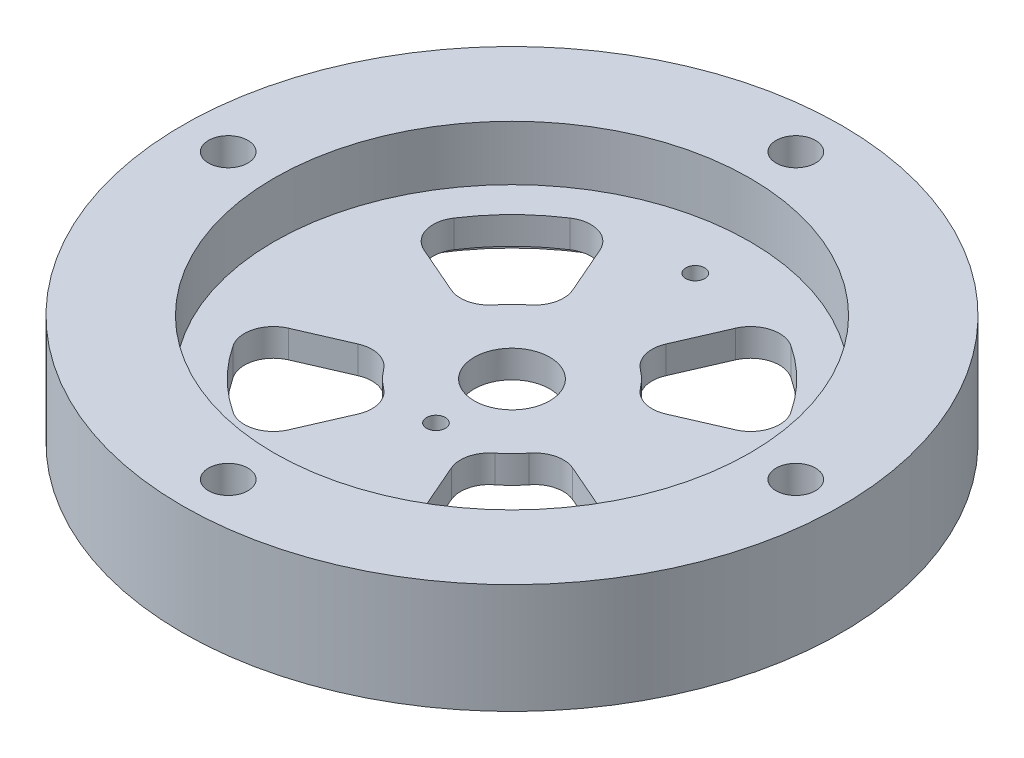
SolidWorks part; units mm, degrees
ref_plane "Front Plane" through (0, 0, 0) normal (0, 0, 1) x (1, 0, 0)
ref_plane "Top Plane" through (0, 0, 0) normal (0, 1, 0) x (1, 0, 0)
ref_plane "Right Plane" through (0, 0, 0) normal (1, 0, 0) x (0, 0, -1)
sketch "Sketch1" plane through (0, 0, 0) normal (0, 0, 1) x (1, 0, 0)
  line L0 (0, 0) -> (0, 12) construction
  line L1 (0, 3) -> (26, 3)
  line L2 (26, 3) -> (26, 0)
  line L3 (36, 12) -> (26, 12)
  line L4 (26, 12) -> (26, 6)
  line L5 (26, 6) -> (0, 6)
  line L6 (0, 6) -> (0, 3)
  line L7 (26, 0) -> (36, 0)
  line L8 (36, 0) -> (36, 12)
  dimension "D1" = 12
  dimension "D2" = 72
  dimension "D3" = 52
  dimension "D4" = 3
  dimension "D5" = 3
  dimension "D6" = 52
revolve "Revolve1" add sketch "Sketch1" angle 360 about L0
sketch "Sketch2" plane through (0, 6, 0) normal (0, 1, 0) x (1, 0, 0)
  line L0 (0, 0) -> (0, 26) construction
  line L1 (0, 0) -> (26, 0) construction
  line L2 (7.3989, 17.0163) -> (5.0987, 11.7262)
  line L3 (17.0163, 7.3989) -> (11.7262, 5.0987)
  line L4 (15.5563, 15.5563) -> (18.3848, 18.3848) construction
  line L5 (5.0987, 11.7262) -> (0, 11.7262) construction
  line L6 (11.7262, 5.0987) -> (11.7262, 0) construction
  line L7 (-7.3989, 17.0163) -> (-5.0987, 11.7262)
  line L8 (-17.0163, 7.3989) -> (-11.7262, 5.0987)
  line L9 (17.0163, -7.3989) -> (11.7262, -5.0987)
  line L10 (7.3989, -17.0163) -> (5.0987, -11.7262)
  line L11 (-7.3989, -17.0163) -> (-5.0987, -11.7262)
  line L12 (-17.0163, -7.3989) -> (-11.7262, -5.0987)
  circle A0 centre (0, 0) radius 26 construction
  arc A1 (12.0496, 18.4067) -> (18.4067, 12.0496) centre (0, 0) cw
  arc A2 (6.08, 7.9394) -> (7.9394, 6.08) centre (0, 0) cw
  arc A3 (7.9394, 6.08) -> (11.7262, 5.0987) centre (10.4602, 8.0104) ccw
  arc A4 (18.4067, 12.0496) -> (17.0163, 7.3989) centre (15.7503, 10.3106) cw
  arc A5 (12.0496, 18.4067) -> (7.3989, 17.0163) centre (10.3106, 15.7503) ccw
  arc A6 (6.08, 7.9394) -> (5.0987, 11.7262) centre (8.0104, 10.4602) cw
  arc A7 (-6.08, 7.9394) -> (-5.0987, 11.7262) centre (-8.0104, 10.4602) ccw
  arc A8 (-6.08, 7.9394) -> (-7.9394, 6.08) centre (0, 0) ccw
  arc A9 (-7.9394, 6.08) -> (-11.7262, 5.0987) centre (-10.4602, 8.0104) cw
  arc A10 (-18.4067, 12.0496) -> (-17.0163, 7.3989) centre (-15.7503, 10.3106) ccw
  arc A11 (-12.0496, 18.4067) -> (-18.4067, 12.0496) centre (0, 0) ccw
  arc A12 (-12.0496, 18.4067) -> (-7.3989, 17.0163) centre (-10.3106, 15.7503) cw
  arc A13 (6.08, -7.9394) -> (5.0987, -11.7262) centre (8.0104, -10.4602) ccw
  arc A14 (6.08, -7.9394) -> (7.9394, -6.08) centre (0, 0) ccw
  arc A15 (7.9394, -6.08) -> (11.7262, -5.0987) centre (10.4602, -8.0104) cw
  arc A16 (18.4067, -12.0496) -> (17.0163, -7.3989) centre (15.7503, -10.3106) ccw
  arc A17 (12.0496, -18.4067) -> (18.4067, -12.0496) centre (0, 0) ccw
  arc A18 (12.0496, -18.4067) -> (7.3989, -17.0163) centre (10.3106, -15.7503) cw
  arc A19 (-12.0496, -18.4067) -> (-7.3989, -17.0163) centre (-10.3106, -15.7503) ccw
  arc A20 (-6.08, -7.9394) -> (-5.0987, -11.7262) centre (-8.0104, -10.4602) cw
  arc A21 (-6.08, -7.9394) -> (-7.9394, -6.08) centre (0, 0) cw
  arc A22 (-7.9394, -6.08) -> (-11.7262, -5.0987) centre (-10.4602, -8.0104) ccw
  arc A23 (-12.0496, -18.4067) -> (-18.4067, -12.0496) centre (0, 0) cw
  arc A24 (-18.4067, -12.0496) -> (-17.0163, -7.3989) centre (-15.7503, -10.3106) cw
  dimension "D1" = 4
  dimension "D3" = 10
  dimension "D4" = 3.175
  dimension "D2" = 43
extrude "Cut-Extrude1" cut sketch "Sketch2" against normal up to next
hole_wizard "#18 (0.1695) Diameter Hole1" positions "Sketch4" profile "Sketch3" hole size "#18" standard "ANSI Inch"
sketch "Sketch4" plane through (0, 12, 0) normal (0, 1, 0) x (1, 0, 0)
  line L0 (0, 26) -> (0, 36) construction
  line L1 (0, 31) -> (0, -31) construction
  line L4 (-31, 0) -> (31, 0) construction
  circle A0 centre (0, 0) radius 26 construction
  circle A2 centre (0, 0) radius 36 construction
  point P10 (0, 31)
  point P28 (0, -31)
  point P33 (-31, 0)
  point P34 (31, 0)
sketch "Sketch3" plane through (0, 12, -31) normal (1, 0, 0) x (0, 0, 1)
  line L0 (0, 0) -> (0, 382.2934)
  line L1 (0, 382.2934) -> (2.1526, 381)
  line L2 (2.1526, 381) -> (2.1526, 0)
  line L5 (2.1526, 0) -> (0, 0)
  line L10 (0, 382.2934) -> (-2.1527, 381) construction
  line L11 (0, -6.35) -> (0, 107.95) construction
  dimension "Hole Dia." = 4.3053
  dimension "Hole Depth" = 381
  dimension "Drill Angle" = 118
sketch "Sketch5" plane through (0, 6, 0) normal (0, 1, 0) x (1, 0, 0)
  circle A0 centre (0, 0) radius 4.1275
  dimension "D1" = 8.255
extrude "Cut-Extrude2" cut sketch "Sketch5" against normal up to next
hole_wizard "CSK for #1 Flat Head Machine Screw (100)1" positions "Sketch6" profile "Sketch7" countersink size "#1" standard "ANSI Inch"
sketch "Sketch6" plane through (0, 3, 0) normal (0, -1, 0) x (0, 0, -1)
  circle A1 centre (-8.3058, 0) radius 1.016
  circle A3 centre (20.0152, 0) radius 1.016
  point P0 (20.0152, 0)
  point P4 (-8.3058, 0)
sketch "Sketch7" plane through (0, 3, -20.0152) normal (1, 0, 0) x (0, 0, -1)
  line L0 (0, 0) -> (0, 3.6181)
  line L1 (0, 3.6181) -> (1.0287, 3)
  line L2 (1.0287, 3) -> (1.0287, 0.6927)
  line L3 (1.0287, 0.6927) -> (1.8542, 0)
  line L4 (1.8542, 0) -> (0, 0)
  line L5 (-1.0287, 0.6927) -> (-1.8542, 0) construction
  line L6 (0, 3.6181) -> (-1.0287, 3) construction
  line L7 (0, -6.35) -> (0, 107.95) construction
  dimension "Hole Dia." = 2.0574
  dimension "Hole Depth" = 3
  dimension "Near C'Sink Dia." = 3.7084
  dimension "Near C'Sink Angle" = 100
  dimension "Drill Angle" = 118
